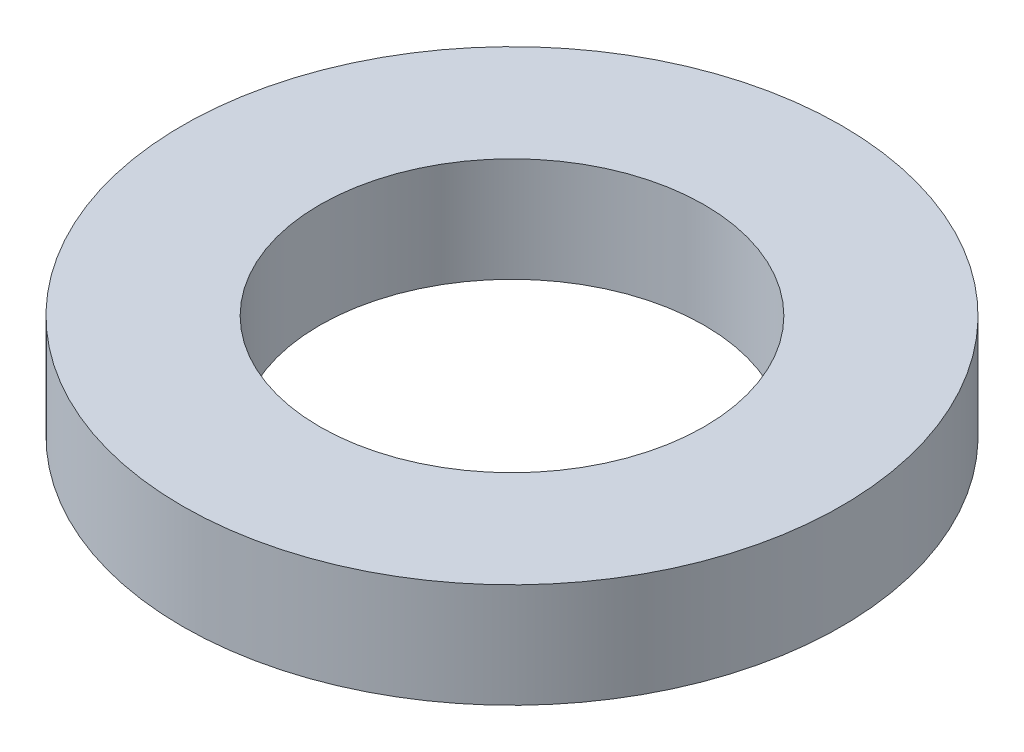
SolidWorks part; units mm, degrees
ref_plane "Front Plane" through (0, 0, 0) normal (0, 0, 1) x (1, 0, 0)
ref_plane "Top Plane" through (0, 0, 0) normal (0, 1, 0) x (1, 0, 0)
ref_plane "Right Plane" through (0, 0, 0) normal (1, 0, 0) x (0, 0, -1)
sketch "Sketch1" plane through (0, 0, 0) normal (0, 1, 0) x (1, 0, 0)
  circle A0 centre (0, 0) radius 60
  dimension "FLANGE_OD" = 120
extrude "Boss-Extrude1" add sketch "Sketch1" along normal blind 19
sketch "Sketch2" plane through (0, 0, 0) normal (0, 1, 0) x (1, 0, 0)
  circle A0 centre (0, 0) radius 35
  dimension "BORE_D" = 70
extrude "Cut-Extrude1" cut sketch "Sketch2" along normal through all
sketch "Sketch3" plane through (0, 19, 0) normal (0, 1, 0) x (1, 0, 0)
  circle A0 centre (0, 0) radius 22.6921 construction
  circle A1 centre (-22.6921, 0) radius 1.8908
  dimension "BOLT_D" = 3.7816
  dimension "BOLT_PCD" = 45.3842
extrude "Cut-Extrude2" cut sketch "Sketch3" against normal blind 12.2029 rebuild error yes
pattern_circular "CirPattern1" count 3 over 360 rebuild error yes
